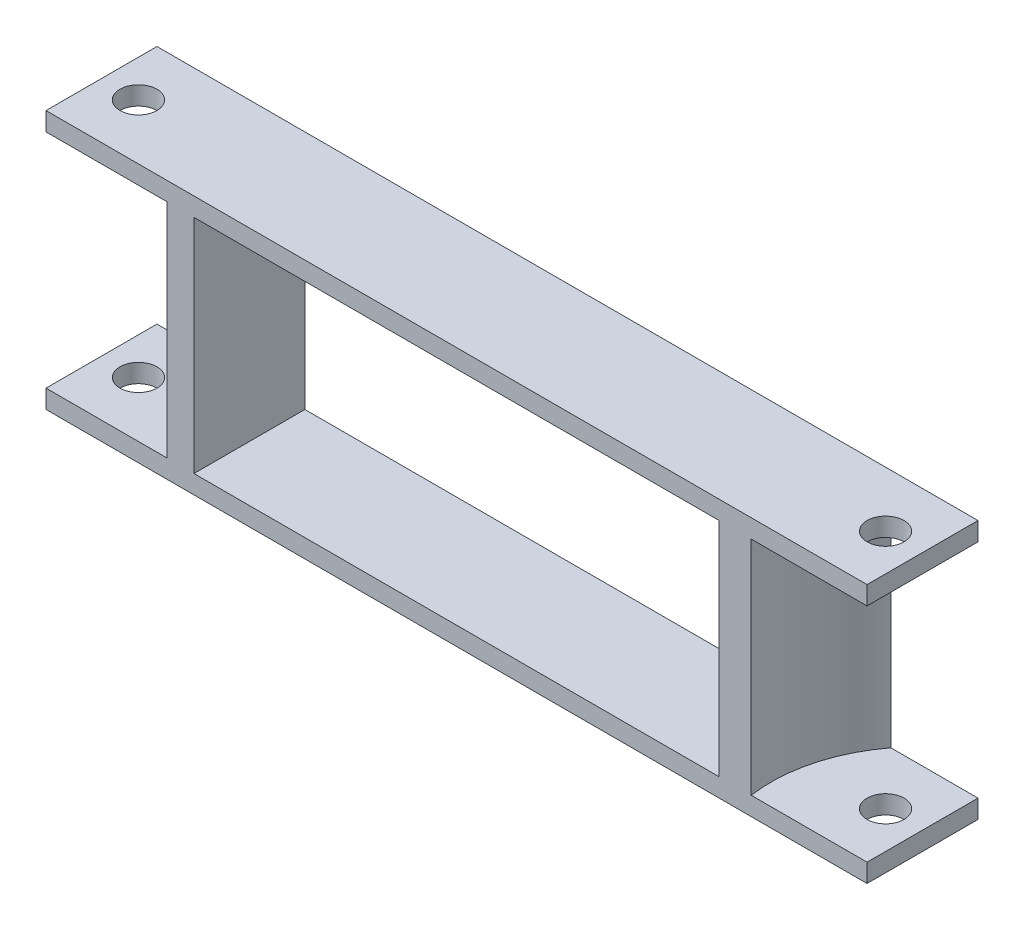
SolidWorks part; units mm, degrees
ref_plane "Alzado" through (0, 0, 0) normal (0, 0, 1) x (1, 0, 0)
ref_plane "Planta" through (0, 0, 0) normal (0, 1, 0) x (1, 0, 0)
ref_plane "Vista lateral" through (0, 0, 0) normal (1, 0, 0) x (0, 0, -1)
sketch "Croquis1" plane through (0, 0, 0) normal (0, 1, 0) x (1, 0, 0)
  line L1 (-36.106, -11.3281) -> (185.894, -11.3281)
  line L2 (-36.106, -11.3281) -> (-36.106, 18.6719)
  line L3 (-36.106, 18.6719) -> (185.894, 18.6719)
  line L4 (185.894, -11.3281) -> (185.894, 18.6719)
  circle A0 centre (-26.106, 3.6719) radius 5
  circle A1 centre (175.894, 3.6719) radius 5
  dimension "D3" = 10
  dimension "D4" = 10
  dimension "D5" = 15
  dimension "D1" = 30
  dimension "D2" = 222
  dimension "D6" = 10
  dimension "D7" = 10
  dimension "D8" = 15
extrude "Saliente-Extruir1" add sketch "Croquis1" along normal blind 70
ref_plane "Plano1" through (0, 35, 0) normal (0, -1, 0) x (-1, 0, 0)
sketch "Croquis2" plane through (0, 35, 0) normal (0, -1, 0) x (-1, 0, 0)
  circle A0 centre (42.3794, -2.3339) radius 40
  circle A1 centre (-194.158, -5.5815) radius 40
  dimension "D1" = 80
  dimension "D2" = 80
extrude "Cortar-Extruir1" cut sketch "Croquis2" against normal blind 30 and the other way blind 30
sketch "Croquis3" plane through (0, 0, 11.3281) normal (0, 0, 1) x (1, 0, 0)
  line L1 (3.894, 65) -> (145.894, 65)
  line L2 (3.894, 65) -> (3.894, 5)
  line L3 (3.894, 5) -> (145.894, 5)
  line L4 (145.894, 65) -> (145.894, 5)
  line L5 (-36.106, 0) -> (185.894, 0) construction
  line L6 (-36.106, 5) -> (-36.106, 0) construction
  dimension "D1" = 60
  dimension "D2" = 142
  dimension "D3" = 40
  dimension "D4" = 5
extrude "Cortar-Extruir2" cut sketch "Croquis3" against normal through all
ref_axis "z2" through (-26.106, 97.6337, -3.6719) along (0, -1, 0)
ref_axis "z3" through (175.894, 95.3058, -3.6719) along (0, -1, 0)
